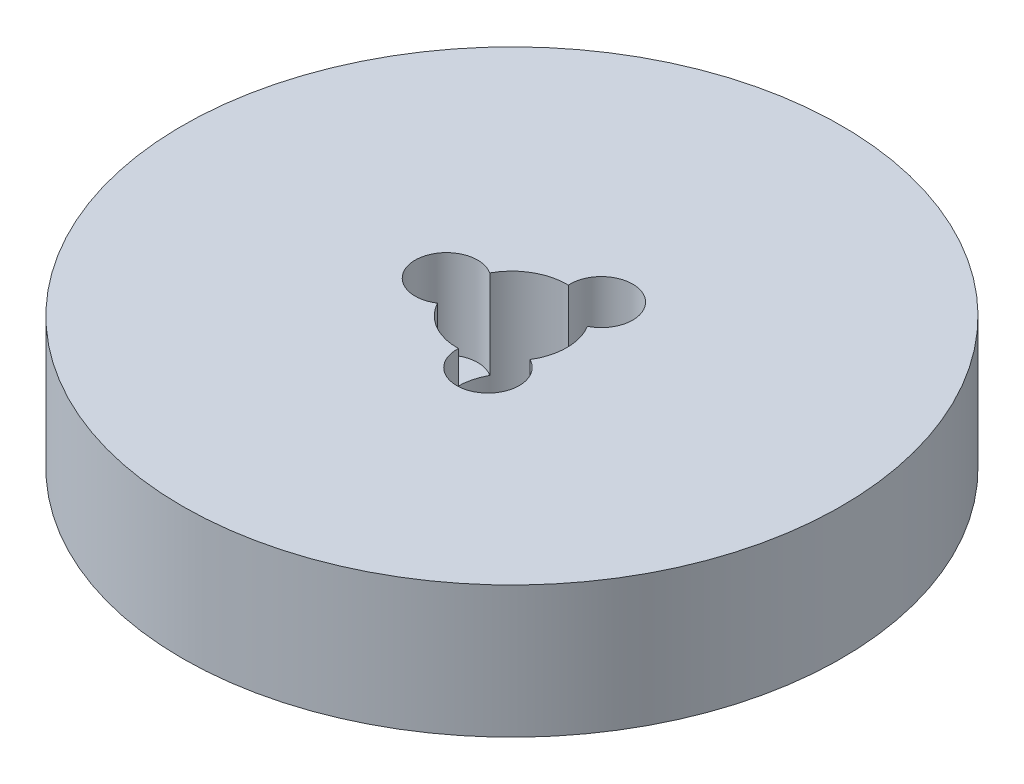
SolidWorks part; units mm, degrees
ref_plane "Front Plane" through (0, 0, 0) normal (0, 0, 1) x (1, 0, 0)
ref_plane "Top Plane" through (0, 0, 0) normal (0, 1, 0) x (1, 0, 0)
ref_plane "Right Plane" through (0, 0, 0) normal (1, 0, 0) x (0, 0, -1)
sketch "Sketch1" plane through (0, 0, 0) normal (0, 1, 0) x (1, 0, 0)
  circle A0 centre (0, 0) radius 60
  dimension "FLANGE_OD" = 120
extrude "Boss-Extrude1" add sketch "Sketch1" along normal blind 24
sketch "Sketch2" plane through (0, 0, 0) normal (0, 1, 0) x (1, 0, 0)
  circle A0 centre (0, 0) radius 10
  dimension "BORE_D" = 20
extrude "Cut-Extrude1" cut sketch "Sketch2" along normal through all
sketch "Sketch3" plane through (0, 24, 0) normal (0, 1, 0) x (1, 0, 0)
  circle A0 centre (0, 0) radius 11.9208 construction
  circle A1 centre (-11.9208, 0) radius 5.6957
  dimension "BOLT_D" = 11.3915
  dimension "BOLT_PCD" = 23.8416
extrude "Cut-Extrude2" cut sketch "Sketch3" against normal blind 16.153
pattern_circular "CirPattern1" count 3 over 360 about axis through (0, 0, 0) along (0, 1, 0) of "Cut-Extrude2"
